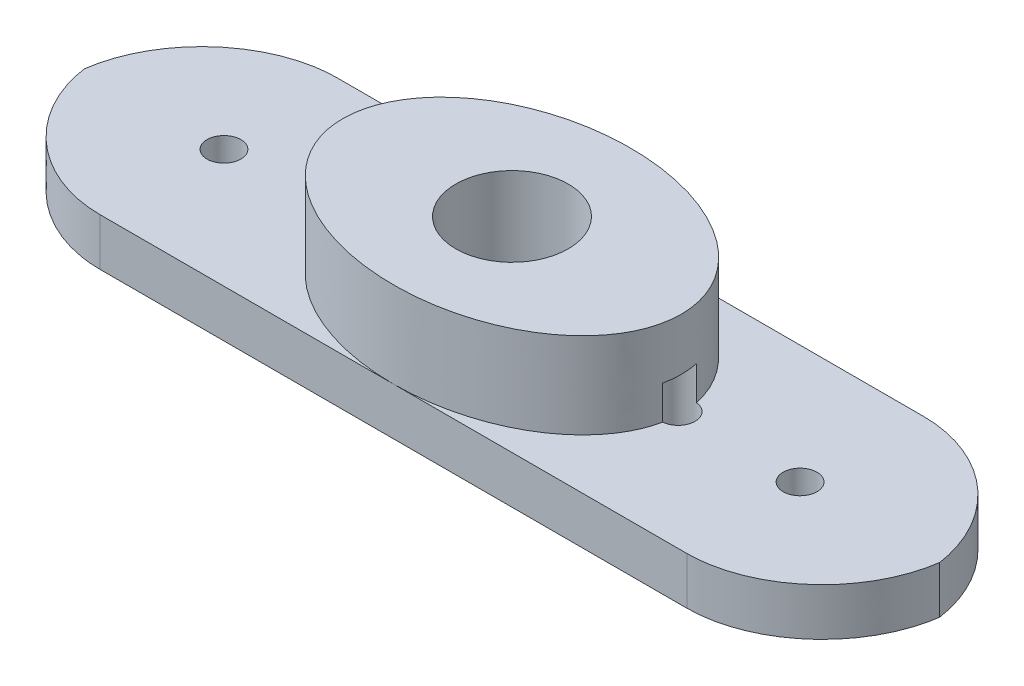
SolidWorks part; units mm, degrees
ref_plane "Front Plane" through (0, 0, 0) normal (0, 0, 1) x (1, 0, 0)
ref_plane "Top Plane" through (0, 0, 0) normal (0, 1, 0) x (1, 0, 0)
ref_plane "Right Plane" through (0, 0, 0) normal (1, 0, 0) x (0, 0, -1)
sketch "Sketch1" plane through (0, 0, 0) normal (0, 1, 0) x (1, 0, 0)
  line L0 (16.0782, 8.89) -> (16.0782, 0) construction
  line L1 (0, 0) -> (32.1564, 0)
  line L2 (0, 0) -> (0, 8.89)
  line L3 (0, 8.89) -> (32.1564, 8.89)
  line L4 (32.1564, 0) -> (32.1564, 8.89)
  circle A0 centre (16.0782, 4.445) radius 1.2319
  circle A2 centre (16.0782, 4.445) radius 2.1082
  ellipse E0 centre (16.0782, 4.445) end of major axis (22.4282, 4.445) minor radius 4.445
  point P7 (0, 0)
  dimension "D3" = 2.4638
  dimension "D4" = 4.2164
  dimension "D5" = 16.0782
  dimension "D6" = 8.89
  dimension "D1" = 6.35
  dimension "D2" = 4.445
extrude "Boss-Extrude1" add sketch "Sketch1" along normal blind 1.778 contours L0 L3 L2 L1 | L3 L0 L1 L4 | L0 A2 | L0 A2 | A2 L0 A0 | L0 A2 A0 region at (19.1097, 0, -4.445) region at (5.636, 0, -4.445) region at (26.5204, 0, -4.445) region at (13.0467, 0, -4.445) region at (17.5356, 0, -5.9024) region at (16.0311, 0, -6.115)
extrude "Cut-Extrude1" cut sketch "Sketch1<5>" along normal through all both and the other way through all from offset 2 contours A2 L0 A0 | L0 A2 A0 | L0 A0 | A0 L0 region at (17.5356, 0, -5.9024) region at (16.0311, 0, -6.115) region at (16.601, 0, -4.445) region at (15.5554, 0, -4.445)
sketch "Sketch1<5>" plane through (0, 0, 0) normal (0, 1, 0) x (1, 0, 0) same geometry as "Sketch1"
fillet "Fillet1" radius 5.08 4 edges at (32.1564, 0.889, -8.89) (32.1564, 0.889, 0) (0, 0.889, -8.89) (0, 0.889, 0) conic rho 0.4
extrude "Boss-Extrude2" add sketch "Sketch1<7>" along normal blind 5 contours E0
sketch "Sketch1<7>" plane through (0, 0, 0) normal (0, 1, 0) x (1, 0, 0) same geometry as "Sketch1"
extrude "Cut-Extrude2" cut sketch "Sketch1<8>" against normal through all both and the other way through all contours A2 L0 A0 | L0 A2 A0 | A0 region at (17.5356, 0, -5.9024) region at (16.0311, 0, -6.115)
sketch "Sketch1<8>" plane through (0, 0, 0) normal (0, 1, 0) x (1, 0, 0) same geometry as "Sketch1"
sketch "Sketch2" plane through (0, 1.778, 0) normal (0, 1, 0) x (1, 0, 0)
  line L0 (0.0437, 4.4449) -> (32.1127, 4.4449) construction
  line L1 (16.0782, 8.8899) -> (16.0782, 0) construction
  circle A0 centre (9.8481, 4.4449) radius 0.635
  circle A1 centre (5.2761, 4.4449) radius 0.635
  circle A2 centre (22.3083, 4.4449) radius 0.635
  circle A3 centre (26.8803, 4.4449) radius 0.635
  ellipse E0 centre (16.0782, 4.445) end of major axis (22.4282, 4.445) minor radius 4.445 construction
  point P18 (16.0782, 4.4449)
  dimension "D3" = 1.27
  dimension "D4" = 1.27
  dimension "D1" = 5.2324
  dimension "D2" = 9.8044
extrude "Cut-Extrude3" cut sketch "Sketch2" against normal blind 12.7 and the other way blind 1.27
